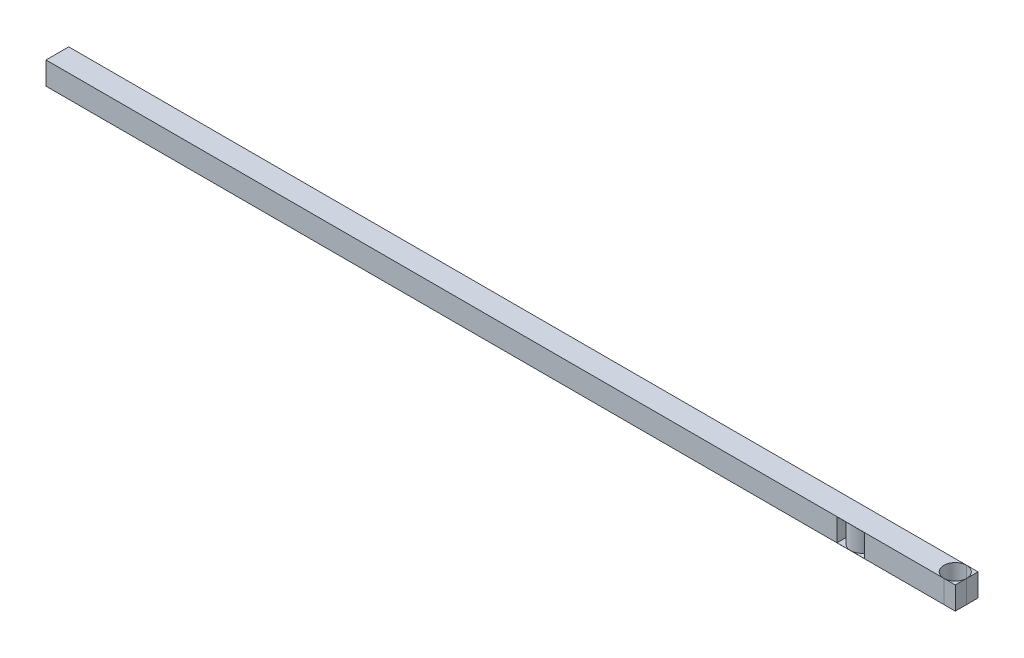
SolidWorks part; units mm, degrees
ref_plane "Front Plane" through (0, 0, 0) normal (0, 0, 1) x (1, 0, 0)
ref_plane "Top Plane" through (0, 0, 0) normal (0, 1, 0) x (1, 0, 0)
ref_plane "Right Plane" through (0, 0, 0) normal (1, 0, 0) x (0, 0, -1)
sketch "Sketch1" plane through (0, 0, 0) normal (0, 0, 1) x (1, 0, 0)
  line L0 (-100, 2) -> (100, 2)
  line L2 (100, -3) -> (-100, -3)
  line L12 (100, 2) -> (100, -3)
  line L13 (-100, 2) -> (-100, -3)
  dimension "D1" = 200
  dimension "D8" = 5
extrude "Boss-Extrude1" add sketch "Sketch1" along normal blind 5
sketch "Sketch3" plane through (0, -3, 0) normal (0, -1, 0) x (1, 0, 0)
  line L0 (-100, 0) -> (100, 0) construction
  circle A0 centre (96.6636, 2.5) radius 2.5
extrude "Boss-Extrude3" add sketch "Sketch3" against normal blind 5
ref_plane "Plane1" through (0, -0.5, 0) normal (0, -1, 0) x (-1, 0, 0)
sketch "Sketch6" plane through (0, 2, 0) normal (0, 1, 0) x (1, 0, 0)
  line L0 (100, -5) -> (100, 0) construction
  line L1 (100, 0) -> (-100, 0) construction
  circle A0 centre (97.5, -2.5) radius 2.5
  dimension "D1" = 5
extrude "Cut-Extrude6" cut sketch "Sketch6" against normal blind 10
sketch "Sketch7" plane through (0, 2, 0) normal (0, 1, 0) x (1, 0, 0)
  line L0 (97.5, 0) -> (-100, 0) construction
  line L1 (-100, -5) -> (-100, 0) construction
  circle A0 centre (-97.5, -2.5) radius 2.5
  dimension "D1" = 5
extrude "Cut-Extrude7" cut sketch "Sketch7" against normal blind 10
sketch "Sketch8" plane through (0, -0.5, 0) normal (0, -1, 0) x (-1, 0, 0)
  line L0 (-100, -5) -> (-100, -2.5) construction
  line L1 (-80, 0.2867) -> (-74, 0.2867)
  line L2 (-80, 0.2867) -> (-80, -5.7133)
  line L3 (-80, -5.7133) -> (-74, -5.7133)
  line L4 (-74, 0.2867) -> (-74, -5.7133)
  dimension "D1" = 6
  dimension "D2" = 6
  dimension "D3" = 20
extrude "Cut-Extrude8" cut sketch "Sketch8" against normal mid plane 4.95
sketch "Sketch9" plane through (0, -2.975, 0) normal (0, 1, 0) x (1, 0, 0)
  line L0 (97.5, 0) -> (-97.5, 0) construction
  line L1 (80, 0) -> (80, -5) construction
  circle A0 centre (77, -2.5) radius 2.5
  dimension "D1" = 5
  dimension "D2" = 3
extrude "Boss-Extrude4" add sketch "Sketch9" along normal up to next
extrude "Boss-Extrude5" add sketch "Sketch7<2>" against normal up to surface (5 mm away) up to face at (0, -3, 2.5)
sketch "Sketch7<2>" plane through (0, 2, 0) normal (0, 1, 0) x (1, 0, 0) same geometry as "Sketch7"
